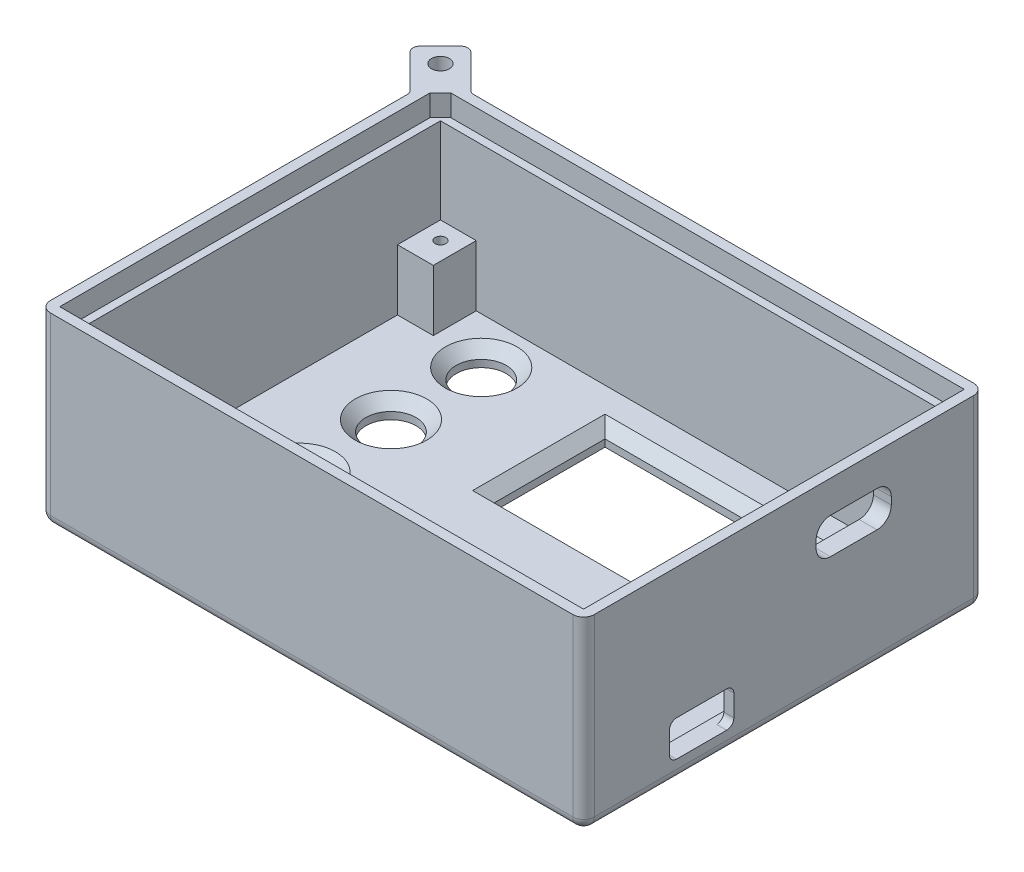
SolidWorks part; units mm, degrees
ref_plane "Front Plane" through (0, 0, 0) normal (0, 0, 1) x (1, 0, 0)
ref_plane "Top Plane" through (0, 0, 0) normal (0, 1, 0) x (1, 0, 0)
ref_plane "Right Plane" through (0, 0, 0) normal (1, 0, 0) x (0, 0, -1)
sketch "Sketch1" plane through (0, 0, 0) normal (0, 1, 0) x (1, 0, 0)
  line L1 (-38, 28) -> (38, 28)
  line L2 (-38, 28) -> (-38, -28)
  line L3 (-38, -28) -> (38, -28)
  line L4 (38, 28) -> (38, -28)
  point P4 (38, 0)
  point P6 (0, 28)
  dimension "D1" = 76
  dimension "D2" = 56
extrude "Boss-Extrude1" add sketch "Sketch1" along normal blind 26
shell "Shell1" thickness 2.5 removed face at (0, 26, 0)
sketch "Sketch2" plane through (0, 2.5, 0) normal (0, 1, 0) x (1, 0, 0)
  line L0 (35.5, 25.5) -> (-35.5, 25.5) construction
  line L1 (-7.5, 20.5) -> (23.75, 20.5)
  line L2 (-7.5, 20.5) -> (-7.5, 5)
  line L3 (-7.5, 5) -> (23.75, 5)
  line L4 (23.75, 20.5) -> (23.75, 5)
  line L6 (38, -28) -> (38, 28) construction
  dimension "D1" = 5
  dimension "D2" = 15.5
  dimension "D3" = 45.5
  dimension "D4" = 14.25
extrude "Cut-Extrude1" cut sketch "Sketch2" against normal through all
sketch "Sketch3" plane through (0, 2.5, 0) normal (0, 1, 0) x (1, 0, 0)
  line L0 (-35.5, 25.5) -> (-35.5, -25.5) construction
  line L1 (35.5, 25.5) -> (-35.5, 25.5) construction
  line L2 (-35.5, 25.5) -> (-35.5, -25.5) construction
  line L3 (-35.5, -25.5) -> (35.5, -25.5) construction
  circle A0 centre (-23.3, 19) radius 3.5
  circle A1 centre (-23.3, -19) radius 3.5
  circle A2 centre (-23.3, 6.3875) radius 3.5
  circle A3 centre (-23.3, -6.3875) radius 3.5
  dimension "D1" = 7
  dimension "D4" = 7
  dimension "D7" = 7
  dimension "D8" = 7
  dimension "D2" = 12.2
  dimension "D3" = 6.5
  dimension "D5" = 12.2
  dimension "D6" = 6.5
  dimension "D9" = 12.2
  dimension "D10" = 12.2
  dimension "D11" = 12.6125
  dimension "D12" = 12.6125
extrude "Cut-Extrude2" cut sketch "Sketch3" against normal through all contours A3 | A2 | A0 | A1 region at (-23.3, 2.5, -19) region at (-23.3, 2.5, 19) region at (-23.3, 2.5, -6.3875) region at (-23.3, 2.5, 6.3875)
sketch "Sketch4" plane through (38, 0, 0) normal (1, 0, 0) x (0, 0, -1)
  line L0 (-28, 26) -> (-28, 0) construction
  line L1 (-16, 7.75) -> (-7, 7.75)
  line L2 (-16, 7.75) -> (-16, 2.75)
  line L3 (-16, 2.75) -> (-7, 2.75)
  line L4 (-7, 7.75) -> (-7, 2.75)
  line L5 (-28, 0) -> (28, 0) construction
  dimension "D1" = 9
  dimension "D2" = 5
  dimension "D3" = 12
  dimension "D4" = 2.75
extrude "Cut-Extrude3" cut sketch "Sketch4" against normal up to next
sketch "Sketch5" plane through (38, 0, 0) normal (1, 0, 0) x (0, 0, -1)
  line L0 (28, 26) -> (28, 0) construction
  line L1 (4.5, 21.5) -> (15, 21.5)
  line L2 (4.5, 21.5) -> (4.5, 16.5)
  line L3 (4.5, 16.5) -> (15, 16.5)
  line L4 (15, 21.5) -> (15, 16.5)
  line L5 (-28, 0) -> (28, 0) construction
  dimension "D1" = 5
  dimension "D2" = 10.5
  dimension "D3" = 13
  dimension "D4" = 21.5
extrude "Cut-Extrude4" cut sketch "Sketch5" against normal up to next
fillet "Fillet1" radius 1 4 edges at (36.75, 2.75, 16) (36.75, 7.75, 16) (36.75, 7.75, 7) (36.75, 2.75, 7)
fillet "Fillet2" radius 2 4 edges at (36.75, 21.5, -15) (36.75, 21.5, -4.5) (36.75, 16.5, -15) (36.75, 16.5, -4.5)
chamfer "Chamfer1" distance 1.5 angle 45 4 edges at (-23.3, 2.5, -15.5) (-23.3, 2.5, -2.8875) (-23.3, 2.5, 9.8875) (-23.3, 2.5, 22.5)
chamfer "Chamfer2" distance 1.5 angle 45 4 edges at (8.125, 2.5, -5) (23.75, 2.5, -12.75) (8.125, 2.5, -20.5) (-7.5, 2.5, -12.75)
fillet "Fillet3" radius 1.5 8 edges at (0, 0, 28) (38, 0, 0) (0, 0, -28) (-38, 0, 0) (-38, 13, -28) (-38, 13, 28) (38, 13, 28) (38, 13, -28)
sketch "Sketch6" plane through (35.5, 0, 0) normal (-1, 0, 0) x (0, 0, 1)
  line L1 (1.5, 2.75) -> (21.5, 2.75)
  line L2 (1.5, 2.75) -> (1.5, 26)
  line L3 (1.5, 26) -> (21.5, 26)
  line L4 (21.5, 2.75) -> (21.5, 26)
  line L7 (25.5, 26) -> (-25.5, 26) construction
  line L8 (8, 7.75) -> (15, 7.75) construction
  line L9 (15, 2.75) -> (8, 2.75) construction
  point P8 (11.5, 26)
  point P9 (11.5, 7.75)
  dimension "D1" = 20
extrude "Cut-Extrude5" cut sketch "Sketch6" against normal blind 1.1
sketch "Sketch7" plane through (0, 26, 0) normal (0, 1, 0) x (1, 0, 0)
  line L0 (35.5, -1.5) -> (35.5, 25.5) construction
  line L1 (-36.6, 26.6) -> (36.6, 26.6)
  line L2 (-36.6, 26.6) -> (-36.6, -26.6)
  line L3 (-36.6, -26.6) -> (36.6, -26.6)
  line L4 (36.6, 26.6) -> (36.6, -26.6)
  line L5 (35.5, 25.5) -> (-35.5, 25.5) construction
  line L6 (-35.5, -25.5) -> (35.5, -25.5) construction
  line L7 (-35.5, 25.5) -> (-35.5, -25.5) construction
  dimension "D1" = 1.1
  dimension "D2" = 1.1
  dimension "D3" = 1.1
  dimension "D4" = 1.1
extrude "Cut-Extrude6" cut sketch "Sketch7" against normal blind 3
sketch "Sketch8" plane through (0, 2.5, 0) normal (0, 1, 0) x (1, 0, 0)
  line L0 (35.5, 25.5) -> (-35.5, 25.5) construction
  line L4 (-35.5, 25.5) -> (-35.5, -25.5) construction
  line L6 (-35.5, 25.5) -> (-30.5, 25.5)
  line L7 (-35.5, 25.5) -> (-35.5, 19.5)
  line L8 (-35.5, 19.5) -> (-30.5, 19.5)
  line L9 (-30.5, 25.5) -> (-30.5, 19.5)
  circle A0 centre (-33, 23) radius 0.75
  line M10 (-35.5, 25.5) -> (-35.5, -25.5)
  line M13 (35.5, 25.5) -> (-35.5, 25.5)
  dimension "D1" = 1.5
  dimension "D2" = 2.5
  dimension "D3" = 2.5
  dimension "D4" = 6
  dimension "D5" = 5
extrude "Boss-Extrude2" add sketch "Sketch8" along normal blind 8.5 contours L9 L8 A0 M13 M10 region at (-33, 2.5, -25.4219)
mirror "Mirror1" about plane through (0, 0, 0) normal (0, 0, 1) of "Boss-Extrude2"
sketch "Sketch9" plane through (0, 2.5, 0) normal (0, 1, 0) x (1, 0, 0)
  line L0 (35.5, -25.5) -> (35.5, 25.5) construction
  line L1 (35.5, 25.5) -> (-35.5, 25.5) construction
  line L2 (35.5, -1.5) -> (35.5, 25.5) construction
  line L3 (30.5, 25.5) -> (35.5, 25.5)
  line L4 (30.5, 25.5) -> (30.5, 20.5)
  line L5 (30.5, 20.5) -> (35.5, 20.5)
  line L6 (35.5, 25.5) -> (35.5, 20.5)
  circle A0 centre (33, 23) radius 0.75
  line M14 (35.5, -25.5) -> (35.5, 25.5)
  line M15 (35.5, 25.5) -> (-30.5, 25.5)
  dimension "D1" = 1.5
  dimension "D2" = 2.5
  dimension "D3" = 2.5
  dimension "D4" = 5
  dimension "D5" = 5
extrude "Boss-Extrude3" add sketch "Sketch9" along normal blind 8.5 contours L4 L5 A0 M14 M15 region at (33, 2.5, -25.4293)
mirror "Mirror2" about plane through (0, 0, 0) normal (0, 0, 1) of "Boss-Extrude3"
sketch "Sketch10" plane through (0, 0, 0) normal (0, -1, 0) x (1, 0, 0)
  line L0 (-38, -23.7574) -> (-33.7574, -28)
  line L1 (-38, -26.5) -> (-38, 26.5) construction
  line L2 (36.5, -28) -> (-36.5, -28) construction
  line L3 (-33.7574, -28) -> (-39.4142, -33.6569)
  line L4 (-39.4142, -33.6569) -> (-43.6569, -29.4142)
  line L5 (-43.6569, -29.4142) -> (-38, -23.7574)
  circle A0 centre (-39.4142, -29.4142) radius 1.25
  dimension "D4" = 2.5
  dimension "D6" = 3
  dimension "D1" = 135
  dimension "D2" = 8
  dimension "D3" = 6
  dimension "D5" = 3
extrude "Boss-Extrude4" add sketch "Sketch10" along normal blind 3 from surface starting at face at (0, 26, 0)
fillet "Fillet4" radius 1 10 edges at (-38, 24.5, -23.7574) (-33.7574, 24.5, -28) (-38, 23, -25.1287) (-37.5607, 23, -27.5607) (-35.1287, 23, -28) (-40.8284, 23, -26.5858) (-36.5858, 23, -30.8284) (-41.5355, 23, -31.5355) (-43.6569, 24.5, -29.4142) (-39.4142, 24.5, -33.6569)
sketch "Sketch14" plane through (0, 0, 0) normal (0, -1, 0) x (1, 0, 0)
  line L0 (35, 24) -> (5, 24) construction
  line L2 (-36.5, 28) -> (36.5, 28) construction
  line L3 (38, 26.5) -> (38, -26.5) construction
  text T0 "DigiClock" font "Poppins" height 3.5
  dimension "D1" = 4
  dimension "D2" = 30
  dimension "D3" = 3
extrude "Cut-Extrude7" cut sketch "Sketch14" against normal blind 1
